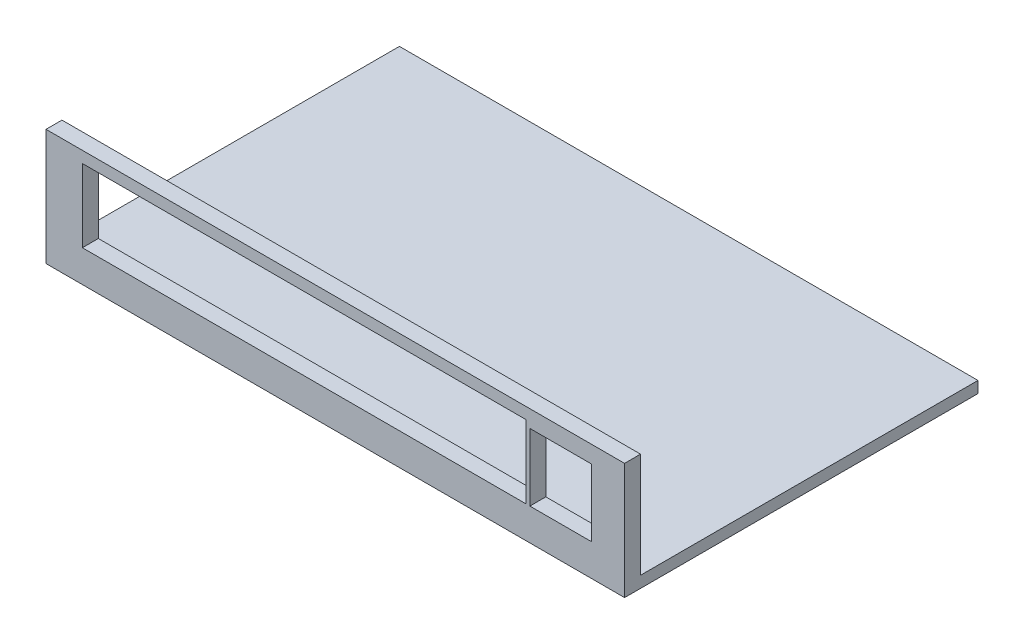
SolidWorks part; units mm, degrees
ref_plane "Front Plane" through (0, 0, 0) normal (0, 0, 1) x (1, 0, 0)
ref_plane "Top Plane" through (0, 0, 0) normal (0, 1, 0) x (1, 0, 0)
ref_plane "Right Plane" through (0, 0, 0) normal (1, 0, 0) x (0, 0, -1)
sketch "Sketch2" plane through (0, 0, 0) normal (0, 1, 0) x (1, 0, 0)
  line L6 (-46.75, -0.5) -> (-46.75, 27.5) construction
  line L7 (-46.75, 27.5) -> (-21.75, 27.5) construction
  line L8 (-46.75, 27.5) -> (46.75, -27.5) construction
  line L9 (-46.75, -27.5) -> (46.75, 27.5) construction
  line L10 (-4.1348, 0) -> (4.1348, 0) construction
  point P8 (0, 0)
  line B0 (-21.75, 27.5) -> (-21.75, -0.5)
  line B1 (46.75, 27.5) -> (-21.75, 27.5)
  line B2 (46.75, -27.5) -> (46.75, 27.5)
  line B3 (-46.75, -27.5) -> (46.75, -27.5)
  line B4 (-46.75, -0.5) -> (-46.75, -27.5)
  line B5 (-21.75, -0.5) -> (-46.75, -0.5)
  line B6 (34.75, -30.5) -> (34.75, -27.5)
  line B7 (34.75, -27.5) -> (44.75, -27.5)
  line B8 (44.75, -27.5) -> (44.75, -30.5)
  line B9 (44.75, -30.5) -> (34.75, -30.5)
  line B10 (-43.75, -30.5) -> (-43.75, -27.5)
  line B11 (-43.75, -27.5) -> (33.25, -27.5)
  line B12 (33.25, -27.5) -> (33.25, -30.5)
  line B13 (33.25, -30.5) -> (-43.75, -30.5)
sketch_block_instance "Block1-1"
sketch_block "Block1"
sketch "Sketch1" plane through (0, 0, 0) normal (0, 1, 0) x (1, 0, 0)
  line L0 (-46.75, -27.5) -> (46.75, -27.5) construction
  line L1 (-50.75, -28.5) -> (50.75, -28.5)
  line L2 (-50.75, -28.5) -> (-50.75, 31.5)
  line L3 (-50.75, 31.5) -> (50.75, 31.5)
  line L4 (50.75, -28.5) -> (50.75, 31.5)
  line L5 (-50.75, -28.5) -> (50.75, 31.5) construction
  line L6 (-50.75, 31.5) -> (50.75, -28.5) construction
  line L7 (-46.75, -0.5) -> (-46.75, -27.5) construction
  line L8 (46.75, -27.5) -> (46.75, 27.5) construction
  line L15 (46.75, 27.5) -> (-21.75, 27.5) construction
  point P0 (0, 0)
  dimension "D1" = 4
  dimension "D2" = 4
  dimension "D3" = 1
  dimension "D4" = 4
extrude "Boss-Extrude1" add sketch "Sketch1" along normal blind 2
sketch "Sketch3" plane through (0, 2, 0) normal (0, 1, 0) x (1, 0, 0)
  line L0 (46.75, 27.5) -> (-21.75, 27.5) construction
  line L1 (-46.75, -0.5) -> (-46.75, -27.5) construction
  line B0 (-21.75, 27.5) -> (-21.75, -0.5)
  line B1 (46.75, 27.5) -> (-21.75, 27.5)
  line B2 (46.75, -27.5) -> (46.75, 27.5)
  line B3 (-46.75, -27.5) -> (46.75, -27.5)
  line B4 (-46.75, -0.5) -> (-46.75, -27.5)
  line B5 (-21.75, -0.5) -> (-46.75, -0.5)
  line B6 (34.75, -30.5) -> (34.75, -27.5)
  line B7 (44.75, -27.5) -> (44.75, -30.5)
  line B8 (44.75, -30.5) -> (34.75, -30.5)
  line B9 (-43.75, -30.5) -> (-43.75, -27.5)
  line B10 (-43.75, -27.5) -> (33.25, -27.5)
  line B11 (33.25, -27.5) -> (33.25, -30.5)
  line B12 (33.25, -30.5) -> (-43.75, -30.5)
sketch_block_instance "Block1-2"
sketch "Sketch5" plane through (0, 2, 0) normal (0, 1, 0) x (1, 0, 0)
  line L16 (50.75, -28.5) -> (50.75, 31.5) construction
  line L17 (-50.75, -28.5) -> (50.75, -28.5)
  line L18 (-50.75, -28.5) -> (-50.75, -30.5)
  line L19 (-50.75, -30.5) -> (50.75, -30.5)
  line L20 (50.75, -28.5) -> (50.75, -30.5)
  line L21 (33.25, -30.5) -> (-43.75, -30.5) construction
extrude "Boss-Extrude2" add sketch "Sketch5" against normal up to surface (2 mm away) up to face at (0, 0, -1.5)
sketch "Sketch7" plane through (0, 0, 30.5) normal (0, 0, 1) x (1, 0, 0)
  line L4 (-43.967, 6) -> (33.033, 6)
  line L5 (33.033, 6) -> (33.033, 18)
  line L6 (33.033, 18) -> (-43.967, 18)
  line L7 (-43.967, 18) -> (-43.967, 6)
  line L8 (-43.967, 6) -> (33.033, 6)
  line L9 (33.033, 6) -> (33.033, 18)
  line L10 (33.033, 18) -> (-43.967, 18)
  line L11 (-43.967, 18) -> (-43.967, 6)
  line L12 (34.533, 6) -> (44.533, 6)
  line L13 (44.533, 6) -> (44.533, 17)
  line L14 (44.533, 17) -> (34.533, 17)
  line L15 (34.533, 17) -> (34.533, 6)
  line L16 (34.533, 6) -> (44.533, 6)
  line L17 (44.533, 6) -> (44.533, 17)
  line L18 (44.533, 17) -> (34.533, 17)
  line L19 (34.533, 17) -> (34.533, 6)
  dimension "D1" = 0
  dimension "D2" = 0
sketch "Sketch8" plane through (0, 0, 30.5) normal (0, 0, 1) x (1, 0, 0)
  line L0 (-43.967, 18) -> (-43.967, 6) construction
  line L1 (-50.75, 2) -> (-44.367, 2)
  line L2 (-50.75, 2) -> (-50.75, 18.4)
  line L3 (-50.75, 18.4) -> (-44.367, 18.4)
  line L4 (-44.367, 2) -> (-44.367, 18.4)
  line L5 (33.033, 18) -> (-43.967, 18) construction
  line L6 (-50.75, 2) -> (50.75, 2) construction
  line L7 (-44.367, 5.6) -> (33.433, 5.6)
  line L8 (-44.367, 5.6) -> (-44.367, 2)
  line L9 (-44.367, 2) -> (33.433, 2)
  line L10 (33.433, 5.6) -> (33.433, 2)
  line L11 (-43.967, 6) -> (33.033, 6) construction
  line L12 (33.033, 6) -> (33.033, 18) construction
  line L13 (34.533, 17) -> (34.533, 6) construction
  line L14 (33.433, 2) -> (34.133, 2)
  line L15 (33.433, 2) -> (33.433, 18.4)
  line L16 (33.433, 18.4) -> (34.133, 18.4)
  line L17 (34.133, 2) -> (34.133, 18.4)
  line L18 (-50.75, 18.4) -> (34.133, 18.4)
  line L19 (-50.75, 18.4) -> (-50.75, 20.4)
  line L20 (-50.75, 20.4) -> (34.133, 20.4)
  line L21 (34.133, 18.4) -> (34.133, 20.4)
  line L22 (50.75, 0) -> (50.75, 2) construction
  line L23 (34.133, 5.6) -> (44.933, 5.6)
  line L24 (34.133, 5.6) -> (34.133, 2)
  line L25 (34.133, 2) -> (44.933, 2)
  line L26 (44.933, 5.6) -> (44.933, 2)
  line L27 (44.933, 2) -> (50.75, 2)
  line L28 (44.933, 2) -> (44.933, 20.4)
  line L29 (44.933, 20.4) -> (50.75, 20.4)
  line L30 (50.75, 2) -> (50.75, 20.4)
  line L31 (34.533, 6) -> (44.533, 6) construction
  line L32 (34.133, 17.4) -> (44.933, 17.4)
  line L33 (34.133, 17.4) -> (34.133, 20.4)
  line L34 (34.133, 20.4) -> (44.933, 20.4)
  line L35 (44.933, 17.4) -> (44.933, 20.4)
  line L36 (44.533, 6) -> (44.533, 17) construction
  line L37 (44.533, 17) -> (34.533, 17) construction
  line M15 (50.75, 2) -> (-50.75, 2)
  dimension "D1" = 0.4
  dimension "D2" = 0.4
  dimension "D3" = 0.4
  dimension "D4" = 0.4
  dimension "D5" = 0.4
  dimension "D6" = 2
  dimension "D7" = 0.4
  dimension "D8" = 0.4
  dimension "D9" = 0.4
extrude "Boss-Extrude3" add sketch "Sketch8" against normal blind 2.8 contours L4 L3 L2 M15 | L16 L21 L20 L19 L3 L18 | L10 L7 L4 M15 | L26 L23 L17 M15 | L17 L16 L15 L10 M15 | L34 L21 L17 L32 L28 | L30 L29 L28 L26 M15 region at (-47.5585, 10.2, 30.5) region at (-5.467, 3.8, 30.5) region at (-8.3085, 19.4, 30.5) region at (33.783, 10.2, 30.5) region at (39.533, 3.8, 30.5) region at (39.533, 18.9, 30.5) region at (47.8415, 11.2, 30.5)
